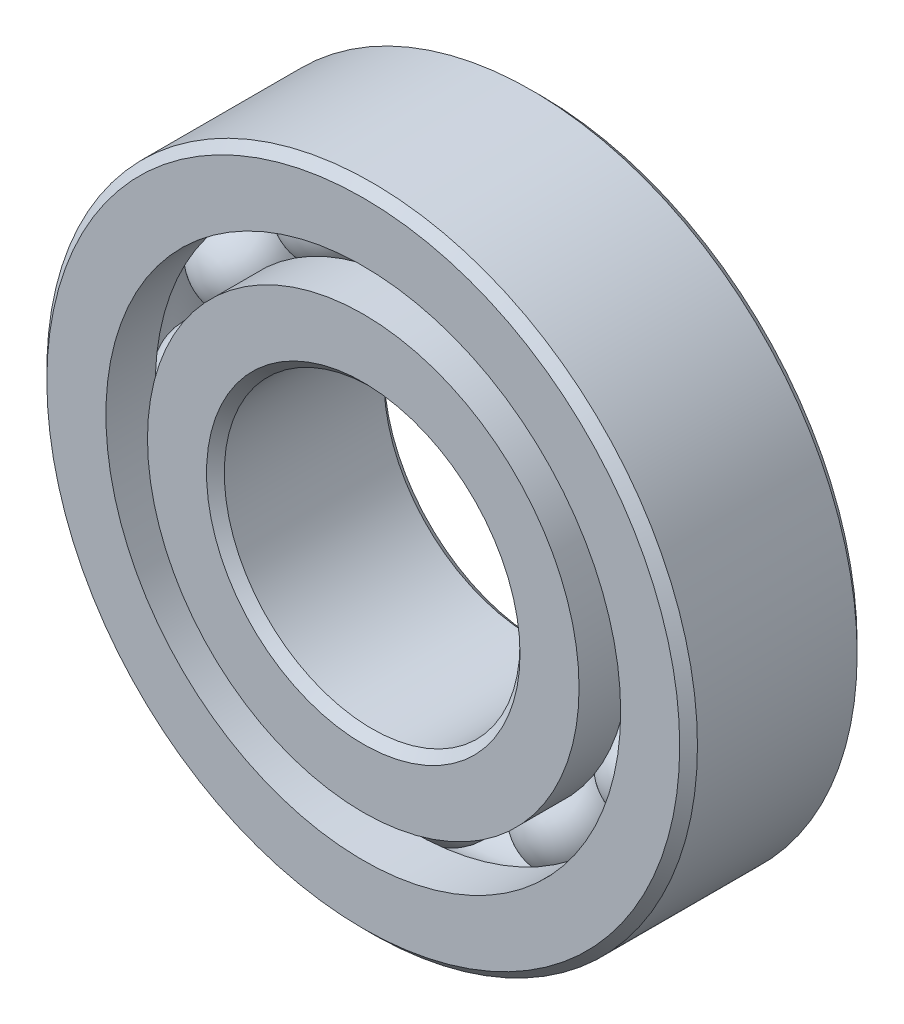
SolidWorks part; units mm, degrees
ref_plane "Front Plane" through (0, 0, 0) normal (0, 0, 1) x (1, 0, 0)
ref_plane "Top Plane" through (0, 0, 0) normal (0, 1, 0) x (1, 0, 0)
ref_plane "Right Plane" through (0, 0, 0) normal (1, 0, 0) x (0, 0, -1)
sketch "Sketch1" plane through (0, 0, 0) normal (1, 0, 0) x (0, 0, -1)
  line L0 (-3, 0) -> (3, 0) construction
  line L1 (0, 11) -> (0, -11) construction
  line L2 (2.7, 11) -> (-2.7, 11)
  line L3 (-2.7, 11) -> (-3, 10.7)
  line L4 (-3, 10.7) -> (-3, 8.7033)
  line L5 (-3, 8.7033) -> (-1.3333, 8.7033)
  line L6 (3, 8.7033) -> (1.3333, 8.7033)
  line L7 (3, 10.7) -> (3, 8.7033)
  line L8 (2.7, 11) -> (3, 10.7)
  line L9 (0, 11) -> (0, 8) construction
  line L10 (0, 8) -> (0, 5) construction
  arc A0 (-1.3333, 8.7033) -> (1.3333, 8.7033) centre (0, 8) cw
  point P14 (0, 5)
  dimension "Width" = 6
  dimension "OD" = 22
  dimension "D1" = 45
  dimension "D2" = 0.3
  dimension "Shaft Dia" = 10
  dimension "D3" = 2.6667
  dimension "D4" = 0.7033
revolve "Revolve1" add sketch "Sketch1" angle 360 about L0
sketch "Sketch3" plane through (0, 0, 0) normal (1, 0, 0) x (0, 0, -1)
  line L0 (-3, 7.2967) -> (-1.3333, 7.2967)
  line L1 (0, 11) -> (0, -11) construction
  line L2 (-3, 10.7) -> (-3, 8.7033) construction
  line L3 (-3, 7.2967) -> (-3, 5.3)
  line L4 (-2.7, 11) -> (-3, 10.7) construction
  line L5 (-3, 5.3) -> (-2.7, 5)
  line L6 (-2.7, 5) -> (2.7, 5)
  line L7 (2.7, 11) -> (2.7, -11) construction
  line L8 (2.7, 5) -> (3, 5.3)
  line L9 (3, -10.7) -> (3, 10.7) construction
  line L10 (3, 5.3) -> (3, 7.2967)
  line L11 (3, 7.2967) -> (1.3333, 7.2967)
  line L13 (2.7, 11) -> (3, 10.7) construction
  arc A0 (1.3333, 8.7033) -> (-1.3333, 8.7033) centre (0, 8) ccw construction
  arc A1 (1.3333, 7.2967) -> (-1.3333, 7.2967) centre (0, 8) cw
revolve "Revolve3" add sketch "Sketch3" angle 360 about L0
sketch "Sketch4" plane through (0, 0, 0) normal (1, 0, 0) x (0, 0, -1)
  line L0 (-1.5074, 8) -> (1.5074, 8)
  arc A2 (-1.5074, 8) -> (1.5074, 8) centre (0, 8) cw
  arc A3 (1.3333, 8.7033) -> (-1.3333, 8.7033) centre (0, 8) ccw construction
revolve "Revolve4" add sketch "Sketch4" angle 360 about L0
ref_axis "Axis1" through (0, 0, -3) along (0, 0, 1)
pattern_circular "CirPattern1" count 12 every 30 about axis through (0, 0, -3) along (0, 0, 1) of bodies 104
sketch "Sketch5" plane through (0, 0, 0) normal (1, 0, 0) x (0, 0, -1)
  line L0 (-3, 8.7033) -> (-1.3333, 8.7033) construction
  line L1 (-2.85, 8.7033) -> (-1.5074, 8.7033)
  line L2 (-2.85, 8.7033) -> (-2.85, 7.2967)
  line L3 (-2.85, 7.2967) -> (-1.5074, 7.2967)
  line L4 (-1.5074, 8.7033) -> (-1.5074, 7.2967)
  line L5 (-3, 7.2967) -> (-1.3333, 7.2967) construction
  line L6 (3, 8.7033) -> (1.3333, 8.7033) construction
  line L7 (2.85, 8.7033) -> (1.5074, 8.7033)
  line L8 (2.85, 8.7033) -> (2.85, 7.2967)
  line L9 (2.85, 7.2967) -> (1.5074, 7.2967)
  line L10 (1.5074, 8.7033) -> (1.5074, 7.2967)
  line L11 (3, 7.2967) -> (1.3333, 7.2967) construction
  line L12 (-2.7, 11) -> (-3, 10.7) construction
  point P18 (-2.85, 10.85)
equation "\"D2@Sketch1\" = \"Width@Sketch1\"*.05"
equation "\"D3@Sketch1\" = \"Width@Sketch1\"/2.25"
equation "\"D4@Sketch1\" = (((\"OD@Sketch1\"-\"Width@Sketch1\")/2)/3.25)/3.5"
equation "\"D2@CirPattern1\" = 360/\"Balls@CirPattern1\""
